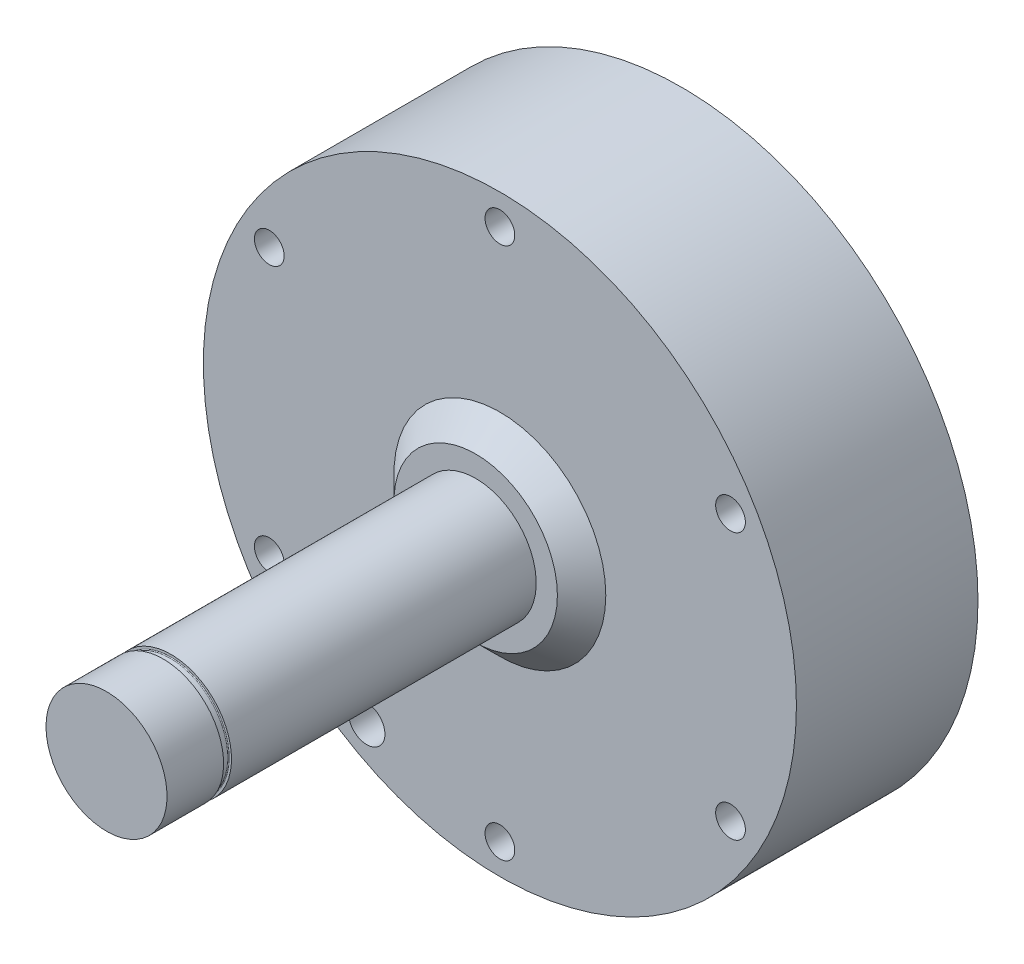
SolidWorks part; units mm, degrees
note: '?' marks a value the reader was unsure of.
ref_plane "Plane1" through (0, 0, 0) normal (0, 0, 1) x (1, 0, 0)
ref_plane "Plane2" through (0, 0, 0) normal (0, 1, 0) x (1, 0, 0)
ref_plane "Plane3" through (0, 0, 0) normal (1, 0, 0) x (0, 0, -1)
sketch "Esquisse1" plane through (0, 0, 0) normal (0, 0, 1) x (1, 0, 0)
  circle A0 centre (0, 0) radius 49
  dimension "D1" = 98
extrude "Base-Extrusion" add sketch "Esquisse1" along normal blind 30
sketch "Esquisse2" plane through (0, 0, 0) normal (1, 0, 0) x (0, 0, -1)
  line L0 (-30, 0) -> (-30, 17.5)
  line L1 (-30, 0) -> (0, 0) construction
  line L2 (-30, 17.5) -> (-34, 13.5)
  line L3 (-34, 13.5) -> (-34, 0)
  line L4 (-34, 0) -> (-30, 0)
  line L5 (-30, 49) -> (-30, -49) construction
  line L6 (-38.8589, 0) -> (34.2943, 0) construction
  dimension "D1" = 4
  dimension "D2" = 45
  dimension "D3" = 17.5
revolve "Boss.-Révol.1" add sketch "Esquisse2" angle 360 about L6
ref_plane "Plan5" through (-49, 0, 15) normal (-1, 0, 0) x (0, 1, 0)
sketch "Esquisse20" plane through (-49, 0, 15) normal (-1, 0, 0) x (0, 1, 0)
  line L1 (-13.5, -19) -> (13.5, -19) construction
  circle A0 centre (0, -3) radius 3
  dimension "D1" = 6
  dimension "D2" = 16
extrude "Enlèv. mat.-Extru.4" cut sketch "Esquisse20" against normal blind 12
sketch "Esquisse3" plane through (0, 0, 34) normal (0, 0, 1) x (1, 0, 0)
  circle A0 centre (0, 0) radius 10
  dimension "D1" = 20
extrude "Boss.-Extru.1" add sketch "Esquisse3" along normal blind 61
sketch "Esquisse11" plane through (0, 0, 30) normal (0, 0, 1) x (1, 0, 0)
  line L0 (0, 0) -> (0, -49) construction
  line L2 (0, 0) -> (-22, -38.1051) construction
  circle A0 centre (-22, -38.1051) radius 3
  circle A1 centre (0, 0) radius 49 construction
  dimension "D3" = 6
  dimension "D1" = 30
  dimension "D2" = 44
extrude "Enlèv. mat.-Extru.3" cut sketch "Esquisse11" against normal through all
hole_wizard "Perçage2" positions "Esquisse13" profile "Esquisse12" legacy
sketch "Esquisse13" plane through (0, 0, 30) normal (0, 0, 1) x (1, 0, 0)
  line L0 (0, -44) -> (0, 0) construction
  line L1 (-22, -38.1051) -> (0, 0) construction
  point P0 (0, -44)
  dimension "D1" = 30
  dimension "D2" = 44
sketch "Esquisse12" plane through (0, -44, 30) normal (1, 0, 0) x (0, -1, 0)
  line L0 (0, 0) -> (0, 26.4751)
  line L1 (0, 26.4751) -> (2.455, 25)
  line L2 (2.455, 25) -> (2.455, 0)
  line L4 (2.455, 0) -> (0, 0)
  line L6 (0, 26.4751) -> (-2.455, 25) construction
  line L7 (0, -4.2442) -> (0, 117.3081) construction
  dimension "Diamètre" = 4.91
  dimension "Profondeur" = 25
  dimension "Angle" = 118
cosmetic thread "Représentation de filetage1" parameters "D1"=15, "D2"=6
pattern_circular "Répétition circulaire1" count 6 over 360 about axis through (0, 0, 0) along (0, 0, 1) of "Perçage2"
ref_axis "Axe1" through (0, 0, 80) along (0, 0, -1)?
hole_wizard "Perçage4" positions "Esquisse17" profile "Esquisse16" hole size "M1.6" standard "Ansi Métrique"
sketch "Esquisse17" plane through (0, 0, 0) normal (0, 0, -1) x (-1, 0, 0)
  line L0 (0, 0) -> (21.242, 21.1844) construction
  line L1 (0, 0) -> (21.7629, -37.8131) construction
  point P0 (21.242, 21.1844)
  dimension "D1" = 105
  dimension "D2" = 30
sketch "Esquisse16" plane through (-21.242, 21.1844, 0) normal (1, 0, 0) x (0, 1, 0)
  line L0 (0, 0) -> (0, 21.8026)
  line L1 (0, 21.8026) -> (3, 20)
  line L2 (3, 20) -> (3, 0)
  line L5 (3, 0) -> (0, 0)
  line L10 (0, 21.8026) -> (-3, 20) construction
  line L11 (0, -6.35) -> (0, 107.95) construction
  dimension "Diamètre du perçage" = 6
  dimension "Profondeur du perçage" = 20
  dimension "Angle de pointe" = 118
pattern_circular "Répétition circulaire3" count 2 every 135 of "Perçage4"
hole_wizard "Perçage5" positions "Esquisse19" profile "Esquisse18" tap size "M6x1.0" standard "Ansi Métrique"
sketch "Esquisse19" plane through (0, 0, 0) normal (0, 0, -1) x (-1, 0, 0)
  line L0 (0, 0) -> (30, -0.0508) construction
  point P0 (30, -0.0508)
  dimension "D1" = 30
sketch "Esquisse18" plane through (-30, -0.0508, 0) normal (1, 0, 0) x (0, 1, 0)
  line L0 (0, 0) -> (0, 21.5022)
  line L1 (0, 21.5022) -> (2.5, 20)
  line L2 (2.5, 20) -> (2.5, 0)
  line L5 (2.5, 0) -> (0, 0)
  line L10 (0, 21.5022) -> (-2.5, 20) construction
  line L11 (0, -6.35) -> (0, 107.95) construction
  dimension "Diamètre du perçage" = 5
  dimension "Profondeur du perçage" = 20
  dimension "Angle de pointe" = 118
cosmetic thread "Représentation de filetage2" parameters "D1"=12, "D2"=6
pattern_circular "Répétition circulaire4" count 3 every 120 about axis through (0, 0, 0) along (0, 0, 1) of "Perçage5"
ref_axis "Axe2" through (0, 0, 95) along (0, 0, -1)?
sketch "Esquisse24" plane through (0, 0, 0) normal (1, 0, 0) x (0, 0, -1)
  line L1 (-30, 0) -> (-41, 0) construction
  line L3 (-30, 49) -> (-30, -49) construction
  line L4 (-30, 0) -> (-27, 0) construction
  point P0 (0, 0)
  dimension "D1" = 11
  dimension "D2" = 3
sketch "Esquisse25" plane through (0, 0, 0) normal (1, 0, 0) x (0, 0, -1)
  line L0 (-41, 0) -> (-91, 0) construction
  point P3 (0, 0)
  dimension "D1" = 50
sketch "Esquisse26" plane through (0, 0, 0) normal (1, 0, 0) x (0, 0, -1)
  line L0 (-30, 0) -> (30, 0) construction
  dimension "D1" = 60
sketch3d "3DSketch1"
  point P0 (6.0594, 7.9551, 0.8549)
ref_axis "Axis1" through (0, 0, 95) along (0, 0, -1)?
ref_plane "Plane5" through (0, 0, 0) normal (0.7955, -0.6059, 0) x (-0.3322, -0.4362, -0.8363)
sketch "Groove Sketch" plane through (2.7659, 3.6313, 10.621) normal (0.7955, -0.6059, 0) x (-0.5067, -0.6653, 0.5483)
  line L0 (53.0071, -54.9644) -> (53.3166, -54.7615)
  line L1 (53.3166, -54.7615) -> (52.6038, -53.6743)
  line L2 (52.6038, -53.6743) -> (52.2944, -53.8772)
  line L3 (52.2569, -54.0572) -> (52.8271, -54.9269)
  line L4 (26.7805, -32.5239) -> (-19.0714, 37.4162) construction
  line L5 (41.7168, -73.5463) -> (58.4429, -62.5809) construction
  line L6 (50.0798, -68.0636) -> (16.6354, -17.0492) construction
  arc A0 (52.8271, -54.9269) -> (53.0071, -54.9644) centre (52.9358, -54.8556) ccw
  arc A1 (52.2569, -54.0572) -> (52.2944, -53.8772) centre (52.3656, -53.9859) cw
  point P10 (52.542, -54.492)
  dimension "Radius" = 0.13
  dimension "ID" = 19
  dimension "OD" = 20
  dimension "Width" = 1.3
  dimension "Location" = 10
revolve "Retaining Ring Groove" cut sketch "Groove Sketch" angle 360 about L4
other "shaft circlip - normal<1>"
